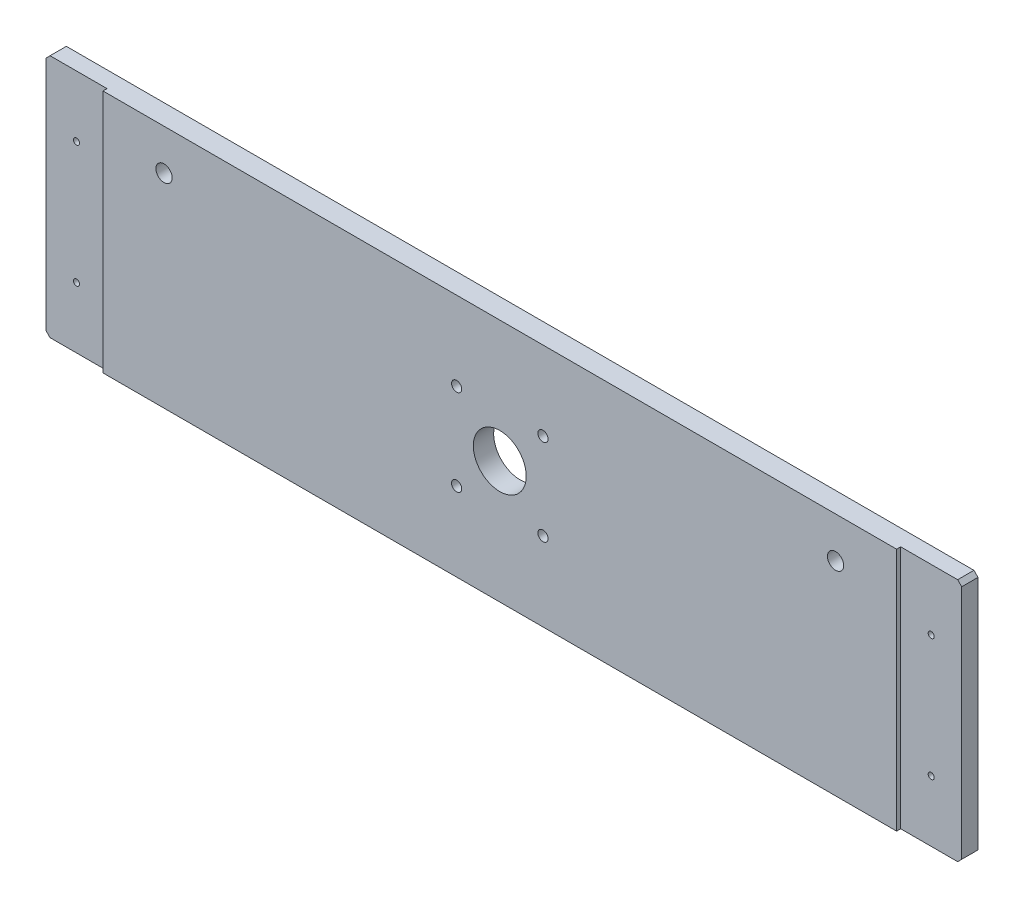
SolidWorks part; units mm, degrees
ref_plane "Piano frontale" through (0, 0, 0) normal (0, 0, 1) x (1, 0, 0)
ref_plane "Piano superiore" through (0, 0, 0) normal (0, 1, 0) x (1, 0, 0)
ref_plane "Piano destro" through (0, 0, 0) normal (1, 0, 0) x (0, 0, -1)
sketch "Schizzo1" plane through (0, 0, 0) normal (0, 0, 1) x (1, 0, 0)
  line L0 (225, 120) -> (225, 0) construction
  line L1 (2, 0) -> (448, 0)
  line L2 (0, 2) -> (0, 118)
  line L3 (2, 120) -> (448, 120)
  line L4 (450, 2) -> (450, 118)
  line L5 (225, 60) -> (199.8765, 85.1235) construction
  line L7 (225, 60) -> (243.5099, 60) construction
  line L8 (459.2931, 100) -> (370.8276, 100) construction
  line L21 (0, 118) -> (2, 120)
  line L22 (2, 0) -> (0, 2)
  line L23 (448, 0) -> (450, 2)
  line L24 (448, 120) -> (450, 118)
  line L25 (225, 60) -> (450, 60) construction
  circle A0 centre (225, 60) radius 13
  circle A1 centre (225, 60) radius 30 construction
  circle A2 centre (246.2132, 81.2132) radius 2.5
  circle A3 centre (390, 100) radius 4
  circle A4 centre (246.2132, 38.7868) radius 2.5
  circle A5 centre (203.7868, 38.7868) radius 2.5
  circle A10 centre (60, 100) radius 4
  circle A11 centre (15, 30) radius 1.5
  circle A12 centre (435, 30) radius 1.5
  circle A13 centre (203.7868, 81.2132) radius 2.5
  circle A17 centre (435, 90) radius 1.5
  circle A18 centre (15, 90) radius 1.5
  point P0 (0, 0)
  point P1 (450, 120)
  point P2 (0, 120)
  point P3 (450, 0)
  point P13 (203.7868, 81.2132)
  point P14 (246.2132, 81.2132)
  point P15 (203.7868, 38.7868)
  point P17 (246.2132, 38.7868)
  dimension "D4" = 26
  dimension "D10" = 8
  dimension "D15" = 3
  dimension "D17" = 5
  dimension "D8" = 60
  dimension "D1" = 120
  dimension "D2" = 450
  dimension "D3" = 60
  dimension "D5" = 45
  dimension "D7" = 20
  dimension "D12" = 60
  dimension "D14" = 30
  dimension "D16" = 15
extrude "Estrusione-Estrusione1" add sketch "Schizzo1" against normal blind 10
sketch "Schizzo2" plane through (0, 0, 0) normal (0, 0, 1) x (1, 0, 0)
  line L0 (448, 120) -> (2, 120) construction
  line L1 (30, 120) -> (0, 120)
  line L2 (30, 120) -> (30, 0)
  line L3 (30, 0) -> (0, 0)
  line L4 (0, 120) -> (0, 0)
  line L5 (225, 120) -> (225, -23.5993) construction
  line L6 (450, 120) -> (450, 0)
  line L7 (420, 0) -> (450, 0)
  line L8 (420, 120) -> (420, 0)
  line L9 (420, 120) -> (450, 120)
  dimension "D1" = 30
extrude "Taglio-Estrusione1" cut sketch "Schizzo2" against normal blind 2
